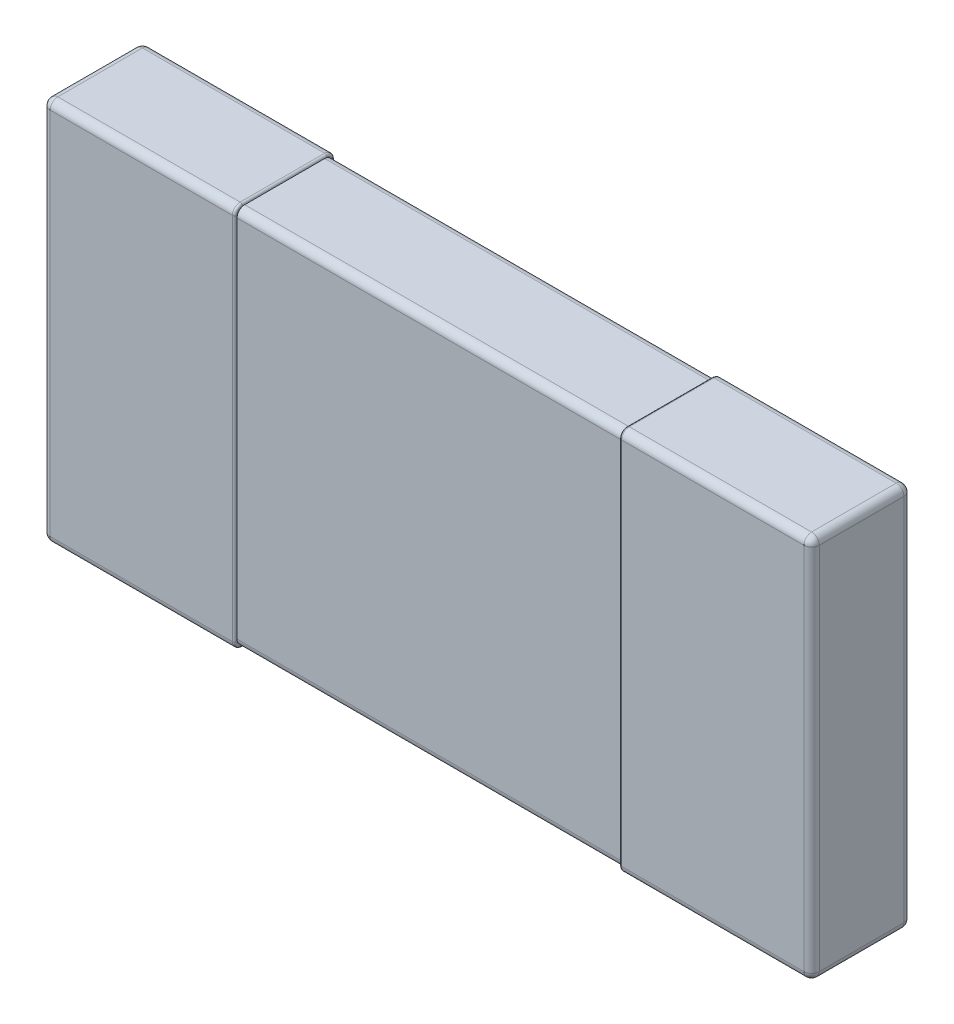
SolidWorks part; units mm, degrees
ref_plane "Top Plane" through (0, 0, 0) normal (0, 0, 1) x (1, 0, 0)
ref_plane "Front Plane" through (0, 0, 0) normal (0, 1, 0) x (1, 0, 0)
ref_plane "Side Plane" through (0, 0, 0) normal (1, 0, 0) x (0, 0, -1)
sketch "Sketch1" plane through (0, 0, 0) normal (0, 0, 1) x (1, 0, 0)
  line L1 (-0.5, 0.25) -> (0.5, 0.25)
  line L2 (-0.5, 0.25) -> (-0.5, -0.25)
  line L3 (-0.5, -0.25) -> (0.5, -0.25)
  line L4 (0.5, 0.25) -> (0.5, -0.25)
  dimension "D1" = 1
  dimension "D2" = 0.5
  dimension "D3" = 0.5
  dimension "D4" = 0.25
extrude "All body" add sketch "Sketch1" along normal blind 0.13
sketch "Sketch2" plane through (0, 0, 0) normal (1, 0, 0) x (0, 0, -1)
  line L14 (-0.003, 0.247) -> (-0.127, 0.247)
  line L15 (-0.003, -0.247) -> (-0.003, 0.247)
  line L16 (-0.127, -0.247) -> (-0.003, -0.247)
  line L17 (-0.127, 0.247) -> (-0.127, -0.247)
  line L18 (-0.003, 0.247) -> (-0.127, 0.247)
  line L19 (-0.003, -0.247) -> (-0.003, 0.247)
  line L20 (-0.127, -0.247) -> (-0.003, -0.247)
  line L21 (-0.127, 0.247) -> (-0.127, -0.247)
  dimension "D1" = 0.003
extrude "Cut out the body for pin" cut sketch "Sketch2" against normal blind 0.25 and the other way blind 0.25 flip side to cut
fillet "Body fillet" radius 0.01 4 edges at (0, 0.247, 0.003) (0, 0.247, 0.127) (0, -0.247, 0.003) (0, -0.247, 0.127)
fillet "Pin fillet a" radius 0.01 16 edges at (0.5, -0.25, 0.065) (0.5, 0, 0.13) (0.5, 0.25, 0.065) (0.5, 0, 0) (-0.5, 0.25, 0.065) (-0.5, 0, 0.13) (-0.5, -0.25, 0.065) (-0.5, 0, 0) (0.375, 0.25, 0.13) (0.375, -0.25, 0.13) (0.375, -0.25, 0) (0.375, 0.25, 0) (-0.375, 0.25, 0) (-0.375, -0.25, 0) (-0.375, 0.25, 0.13) (-0.375, -0.25, 0.13)
fillet "Pin fillet b" radius 0.003 16 edges at (0.25, -0.2471, 0.1271) (0.25, -0.25, 0.065) (0.25, -0.2471, 0.0029) (0.25, 0, 0) (0.25, 0.2471, 0.0029) (0.25, 0.25, 0.065) (0.25, 0.2471, 0.1271) (-0.25, -0.2471, 0.1271) (-0.25, -0.25, 0.065) (-0.25, -0.2471, 0.0029) (-0.25, 0, 0) (-0.25, 0.2471, 0.0029) (-0.25, 0.25, 0.065) (-0.25, 0.2471, 0.1271) (0.25, 0, 0.13) (-0.25, 0, 0.13)
